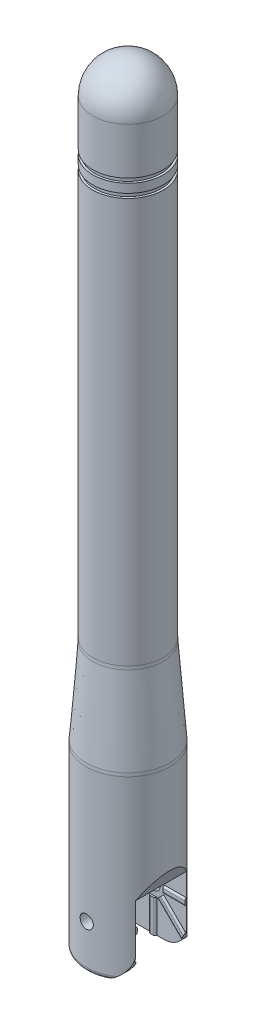
SolidWorks part; units mm, degrees
ref_plane "Plan de face" through (0, 0, 0) normal (0, 0, 1) x (1, 0, 0)
ref_plane "Plan de dessus" through (0, 0, 0) normal (0, 1, 0) x (1, 0, 0)
ref_plane "Plan de droite" through (0, 0, 0) normal (1, 0, 0) x (0, 0, -1)
sketch "Esquisse2" plane through (0, 0, 0) normal (0, 0, 1) x (1, 0, 0)
  line L0 (0, 0) -> (0, 87.9) construction
  line L1 (0, 87.9) -> (4, 87.9) construction
  line L2 (4, 87.9) -> (4, 0) construction
  line L3 (4, 0) -> (0, 0) construction
  line L4 (4, 0) -> (4.75, 0) construction
  line L5 (4.75, 0) -> (4.75, 20.4) construction
  line L6 (4.75, 20.4) -> (0, 20.4) construction
  line L7 (4, 83.9) -> (4, 30.5872) construction
  line L8 (4.014, 30.2133) -> (4.736, 20.5867)
  line L9 (4.75, 20.2128) -> (4.75, 0)
  line L10 (4.75, 0) -> (1, 0)
  line L11 (1, 0) -> (1, 83.9)
  line L12 (1, 83.9) -> (0, 83.9)
  line L13 (4, 83.9) -> (4, 78.6)
  line L14 (4, 78.6) -> (3.75, 78.6)
  line L15 (3.75, 78.6) -> (3.75, 78.1)
  line L16 (3.75, 78.1) -> (4, 78.1)
  line L17 (4, 78.1) -> (4, 77.1)
  line L18 (4, 77.1) -> (3.75, 77.1)
  line L19 (3.75, 77.1) -> (3.75, 76.6)
  line L20 (3.75, 76.6) -> (4, 76.6)
  line L21 (0, 87.9) -> (0, 83.9)
  line L22 (4, 76.6) -> (4, 30.5872)
  arc A0 (0, 87.9) -> (4, 83.9) centre (0, 83.9) cw
  arc A1 (4.75, 20.2128) -> (4.736, 20.5867) centre (-0.25, 20.2128) ccw
  arc A2 (4.014, 30.2133) -> (4, 30.5872) centre (9, 30.5872) cw
  point P18 (4, 30.4)
  point P25 (3.875, 77.1)
  dimension "D7" = 5
  dimension "D1" = 87.9
  dimension "D2" = 8
  dimension "D3" = 9.5
  dimension "D4" = 20.4
  dimension "D5" = 2
  dimension "D6" = 10
  dimension "D8" = 9.3
  dimension "D9" = 0.5
  dimension "D10" = 1.5
  dimension "D11" = 7.5
revolve "Révolution1" add sketch "Esquisse2" angle 360 about L0
sketch "Esquisse3" plane through (0, 0, 0) normal (0, -1, 0) x (1, 0, 0)
  line L0 (0, 0) -> (-2.75, 0) construction
  line L1 (-2.75, 2.9) -> (4.75, 2.9)
  line L2 (-2.75, 2.9) -> (-2.75, -2.9)
  line L3 (-2.75, -2.9) -> (4.75, -2.9)
  line L4 (4.75, 2.9) -> (4.75, -2.9)
  line L5 (-4.75, 0) -> (-2.75, 0) construction
  circle A0 centre (0, 0) radius 4.75 construction
  dimension "D1" = 5.8
  dimension "D2" = 2
extrude "Enlèv. mat.-Extru.1" cut sketch "Esquisse3" against normal blind 8
fillet "Congé1" radius 0.5 1 edges at (-4.75, 0, 0)
sketch "Esquisse4" plane through (0, 0, 0) normal (0, 0, 1) x (1, 0, 0)
  line L0 (3.762, 8) -> (3.762, 0.5) construction
  line L1 (-4.75, 0) -> (3.762, 0) construction
  line L2 (1.162, 0) -> (3.762, 0)
  line L3 (3.762, 0) -> (3.762, 2.6)
  line L4 (0, 0) -> (0, 5) construction
  line L5 (3.762, 8) -> (4.75, 10)
  line L6 (4.75, 8) -> (4.75, 20.2128) construction
  line L7 (4.75, 10) -> (4.75, 8)
  line L8 (3.762, 8) -> (4.75, 8) construction
  line L9 (4.75, 8) -> (3.762, 8)
  arc A0 (3.762, 2.6) -> (1.162, 0) centre (1.162, 2.6) cw
  circle A1 centre (0, 5) radius 0.75
  dimension "D1" = 2.6
  dimension "D3" = 1.5
  dimension "D2" = 5
  dimension "D4" = 2
extrude "Enlèv. mat.-Extru.2" cut sketch "Esquisse4" against normal through all both and the other way through all
sketch "Esquisse5" plane through (0, 0, -2.9) normal (0, 0, 1) x (1, 0, 0)
  line L0 (-4.25, 0) -> (1.162, 0) construction
  line L1 (-0.375, 0) -> (0.375, 0)
  line L2 (-0.375, 0) -> (-0.375, 3.75)
  line L3 (-0.375, 3.75) -> (0.375, 3.75)
  line L4 (0.375, 0) -> (0.375, 3.75)
  line L5 (0, 5) -> (0, 3.75) construction
  line L6 (0, 5) -> (3.762, 1.238) construction
  line L7 (3.762, 8) -> (3.762, 2.6) construction
  line L8 (0.6187, 3.851) -> (3.4968, 0.9729) construction
  line L9 (0.6187, 3.851) -> (1.149, 4.3813)
  line L10 (3.4968, 0.9729) -> (4.0271, 1.5032)
  line L11 (1.149, 4.3813) -> (4.0271, 1.5032) construction
  line L12 (0.6187, 3.851) -> (4.0271, 1.5032) construction
  line L13 (3.4968, 0.9729) -> (1.149, 4.3813) construction
  line L14 (1.149, 4.3813) -> (4.0271, 1.5032)
  line L15 (0.6187, 3.851) -> (3.4968, 0.9729)
  line L16 (0, 5) -> (3.762, 5) construction
  line L18 (1.25, 4.625) -> (3.762, 4.625)
  line L19 (1.25, 4.625) -> (1.25, 5.375)
  line L20 (1.25, 5.375) -> (3.762, 5.375)
  line L21 (3.762, 4.625) -> (3.762, 5.375)
  line L22 (1.25, 4.625) -> (3.762, 5.375) construction
  line L23 (1.25, 5.375) -> (3.762, 4.625) construction
  point P13 (2.3229, 2.6771)
  point P18 (2.506, 5)
  dimension "D1" = 0.75
  dimension "D2" = 1.25
  dimension "D3" = 45
  dimension "D4" = 1.25
  dimension "D5" = 1.25
extrude "Boss.-Extru.1" add sketch "Esquisse5" along normal blind 0.2
fillet "Congé2" radius 0.2 6 edges at (2.506, 5.375, -2.7) (2.506, 4.625, -2.7) (2.5881, 2.9422, -2.7) (2.0578, 2.4119, -2.7) (-0.375, 1.875, -2.7) (0.375, 1.875, -2.7)
mirror "Symétrie1" about plane through (0, 0, 0) normal (0, 0, 1) of "Congé2", "Boss.-Extru.1"
sketch "Esquisse6" plane through (0, 0, 2.9) normal (0, 0, 1) x (1, 0, 0)
  line L3 (4.0271, 1.5032) -> (3.6581, 1.8723)
  line L4 (3.3199, 1.1497) -> (3.4968, 0.9729)
  line L5 (3.4968, 0.9729) -> (4.0271, 1.5032)
  line L6 (4.0271, 1.5032) -> (3.6581, 1.8723)
  line L7 (3.3199, 1.1497) -> (3.4968, 0.9729)
  line L8 (3.4968, 0.9729) -> (4.0271, 1.5032)
  arc A1 (3.3199, 1.1497) -> (3.6581, 1.8723) centre (1.162, 2.6) ccw
  arc A2 (3.3199, 1.1497) -> (3.6581, 1.8723) centre (1.162, 2.6) ccw
  dimension "D1" = 0
extrude "Enlèv. mat.-Extru.3" cut sketch "Esquisse6" against normal through all
